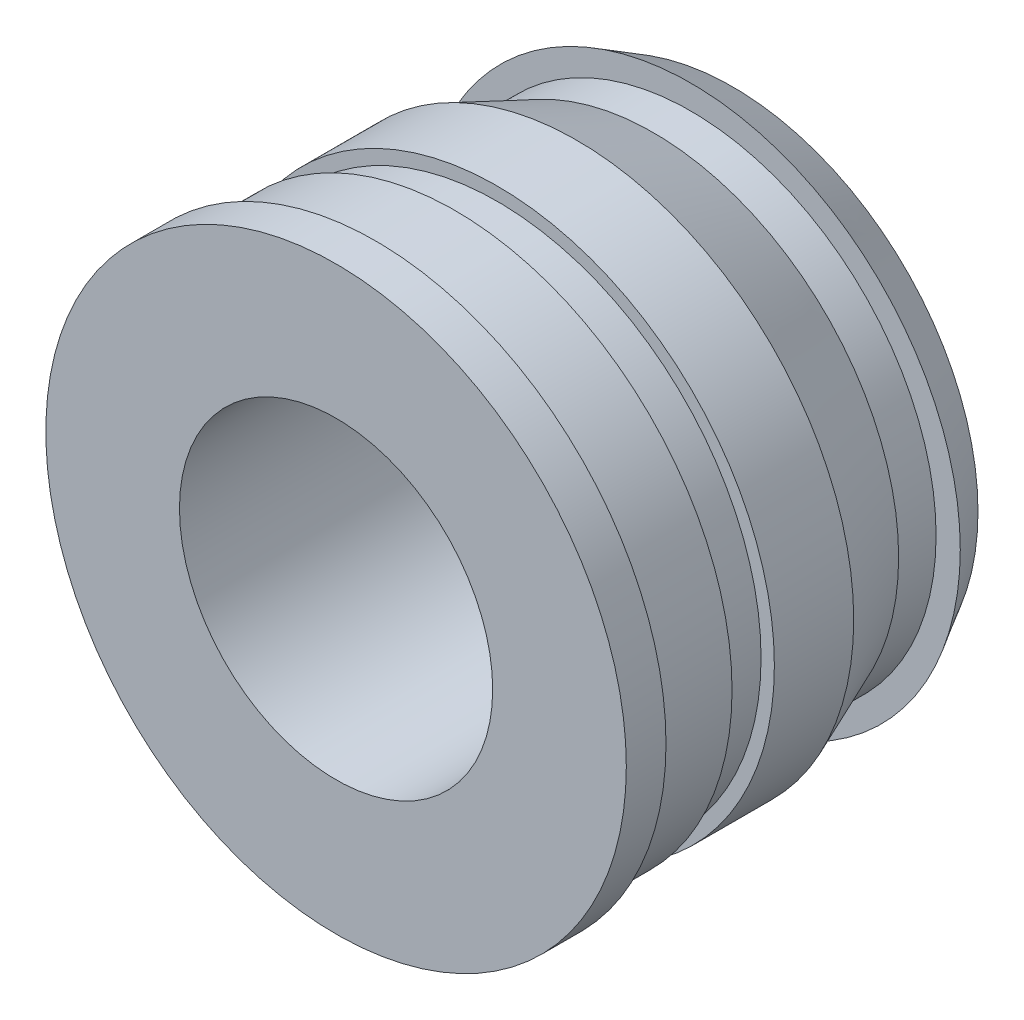
SolidWorks part; units mm, degrees
material "Brass"
ref_plane "Front Plane" through (0, 0, 0) normal (0, 0, 1) x (1, 0, 0)
ref_plane "Top Plane" through (0, 0, 0) normal (0, 1, 0) x (1, 0, 0)
ref_plane "Right Plane" through (0, 0, 0) normal (1, 0, 0) x (0, 0, -1)
sketch "Sketch1" plane through (0, 0, 0) normal (1, 0, 0) x (0, 0, -1)
  line L0 (-1.9, 0) -> (1.9, 0) construction
  line L1 (-1.9, 1.5) -> (-1.9, 2.78)
  line L2 (-1.9, 2.78) -> (-1.52, 2.78)
  line L3 (-1.52, 2.78) -> (-1.52, 2.6525)
  line L4 (-1.52, 2.6525) -> (-0.76, 2.6525)
  line L5 (-0.76, 2.6525) -> (-0.76, 2.525)
  line L6 (-0.76, 2.525) -> (-0.3545, 2.525)
  line L7 (-0.3545, 2.525) -> (-0.3545, 2.6525)
  line L9 (0.4055, 2.6525) -> (1.14, 2.3482)
  line L13 (1.14, 2.3482) -> (1.4986, 2.3482)
  line L14 (1.4986, 2.3482) -> (1.4986, 2.58)
  line L15 (1.4986, 2.58) -> (1.9, 2.3482)
  line L16 (1.9, 2.3482) -> (1.9, 1.5)
  line L17 (-1.9, 2.58) -> (1.9, 2.58) construction
  line L18 (1.9, 0) -> (1.9, 2.58) construction
  line L19 (-1.9, 0) -> (-1.9, 2.78) construction
  line L20 (-0.3545, 2.6525) -> (0.4055, 2.6525)
  line L21 (-1.9, 1.5) -> (1.9, 1.5)
  line L23 (-2.3688, 1.5541) -> (-2.1187, 1.1211) construction
  line L24 (-1.9, -2.58) -> (1.9, -2.58) construction
  line L25 (-2.1187, 1.1211) -> (-1.8687, 1.5541) construction
  line L26 (-1.8687, 1.5541) -> (-2.3688, 1.5541) construction
  line L27 (-2.3375, 1.5) -> (-1.9, 1.5) construction
  line L28 (-2.1187, 1.5541) -> (-2.1187, 1.5) construction
  line L29 (-2.1187, 1.5) -> (-2.1187, 1.1752) construction
  line L30 (-2.1187, 1.1752) -> (-2.1187, 1.1211) construction
  line L31 (-2.15, 1.1752) -> (-2.0875, 1.1752)
  line L32 (-2.3531, 1.5271) -> (-1.8844, 1.5271)
  line L33 (-2.0875, 1.1752) -> (-1.8844, 1.5271)
  line L34 (-2.15, 1.1752) -> (-2.3531, 1.5271)
  line L35 (-1.9, 2.525) -> (1.9, 2.525) construction
  line L36 (-1.9, -2.525) -> (1.9, -2.525) construction
  point P36 (-2.1187, 1.5271)
  dimension "Installed Length" = 3.8
  dimension "Dia A" = 5.56
  dimension "Dia B" = 5.16
  dimension "Thread Dia" = 3
  dimension "D6" = 30
  dimension "D8" = 0.76
  dimension "D4" = 22.5
  dimension "Thread Pitch" = 0.5
  dimension "D2" = 0.0625
  dimension "Max Hole Dia" = 5.05
  dimension "Knurling Length" = 2.66
  dimension "D1" = 4.6965
  dimension "D3" = 0.38
ref_plane "Plane1" through (0, 0, 1.52) normal (0, 0, 1) x (1, 0, 0)
sketch "Sketch2" plane through (0, 0, 1.52) normal (0, 0, 1) x (1, 0, 0)
  line L0 (0, 0) -> (0, 2.6525) construction
  line L1 (-0.1988, 2.6551) -> (0, 2.525)
  line L2 (0.1988, 2.6551) -> (0, 2.525)
  line L3 (-0.185, 2.646) -> (0, 0) construction
  line L4 (0.185, 2.646) -> (0, 0) construction
  line L5 (0, 0) -> (-0.3462, 2.6298) construction
  line L6 (0, 0) -> (0.3462, 2.6298) construction
  line L7 (0, 0) -> (1.8756, 1.8756) construction
  line L8 (0, 0) -> (0, -1.5541) construction
  line L9 (0, 0) -> (0.7771, -1.3459) construction
  circle A0 centre (0, 0) radius 2.525 construction
  circle A1 centre (0, 0) radius 2.6525 construction
  circle A3 centre (0, 0) radius 1.5541
  arc A4 (-0.1988, 2.6551) -> (0.1988, 2.6551) centre (0, 0) cw
  dimension "Knurl Angle" = 8
  dimension "Pattern Angle" = 15
  dimension "Helix Angle" = 45
  dimension "D1" = 30
sketch "Sketch3" plane through (0, 0, 0) normal (1, 0, 0) x (0, 0, -1)
  line L0 (-1.9, 1.5) -> (-1.9, 2.78) construction
  line L1 (-1.9, 2.78) -> (-1.52, 2.78) construction
  line L2 (-1.52, 2.78) -> (-1.52, 2.6525) construction
  line L3 (-1.52, 2.6525) -> (-0.76, 2.6525) construction
  line L4 (-0.76, 2.6525) -> (-0.76, 2.525) construction
  line L5 (-0.76, 2.525) -> (-0.3545, 2.525) construction
  line L6 (-0.3545, 2.525) -> (-0.3545, 2.6525) construction
  line L8 (0.4055, 2.6525) -> (1.14, 2.3482) construction
  line L12 (1.14, 2.3482) -> (1.4986, 2.3482) construction
  line L13 (1.4986, 2.3482) -> (1.4986, 2.58) construction
  line L14 (1.4986, 2.58) -> (1.9, 2.3482) construction
  line L15 (1.9, 2.3482) -> (1.9, 1.5) construction
  line L16 (-1.9, 1.5) -> (1.9, 1.5) construction
  line L17 (-1.9, 1.5) -> (-1.9, 2.78)
  line L18 (-1.9, 2.78) -> (-1.52, 2.78)
  line L19 (-1.52, 2.78) -> (-1.52, 2.6525)
  line L20 (-1.52, 2.6525) -> (-0.76, 2.6525)
  line L21 (-0.76, 2.6525) -> (-0.76, 2.525)
  line L22 (-0.76, 2.525) -> (-0.3545, 2.525)
  line L23 (-0.3545, 2.525) -> (-0.3545, 2.6525)
  line L25 (0.4055, 2.6525) -> (1.14, 2.3482)
  line L29 (1.14, 2.3482) -> (1.4986, 2.3482)
  line L30 (1.4986, 2.3482) -> (1.4986, 2.58)
  line L31 (1.4986, 2.58) -> (1.9, 2.3482)
  line L32 (1.9, 2.3482) -> (1.9, 1.5)
  line L33 (-1.9, 1.5) -> (1.9, 1.5)
  line L34 (-0.3545, 2.6525) -> (0.4055, 2.6525) construction
  line L35 (-0.3545, 2.6525) -> (0.4055, 2.6525)
revolve "Revolve1" add sketch "Sketch3" angle 360 about L0
sketch "Sketch4" [suppressed] plane through (0, 0, 1.52) normal (0, 0, 1) x (1, 0, 0)
  circle A2 centre (0, 0) radius 2.6525 construction
  circle A3 centre (0, 0) radius 2.6525
sketch "Sketch6" [suppressed] plane through (0, 0, 1.9) normal (0, 0, 1) x (1, 0, 0)
  circle A0 centre (0, 0) radius 1.5
curve "Helix/Spiral2" [suppressed] pitch 0.5 height 4.3 turns 8.6
sketch "Sketch7" [suppressed] plane through (0, 0, 0) normal (1, 0, 0) x (0, 0, -1)
  line L0 (-2.15, 1.1752) -> (-2.0875, 1.1752) construction
  line L1 (-2.15, 1.1752) -> (-2.3531, 1.5271) construction
  line L2 (-2.3531, 1.5271) -> (-1.8844, 1.5271) construction
  line L3 (-2.0875, 1.1752) -> (-1.8844, 1.5271) construction
  line L4 (-2.15, 1.1752) -> (-2.0875, 1.1752)
  line L5 (-2.15, 1.1752) -> (-2.3531, 1.5271)
  line L6 (-2.3531, 1.5271) -> (-1.8844, 1.5271)
  line L7 (-2.0875, 1.1752) -> (-1.8844, 1.5271)
sweep "Sweep1" [suppressed] add profiles "Sketch7" path "Helix/Spiral2"
sketch "Sketch8" [suppressed] plane through (0, 0, 1.9) normal (0, 0, 1) x (1, 0, 0)
  circle A0 centre (0, 0) radius 1.5541
extrude "Cut-Extrude1" [suppressed] cut sketch "Sketch8" against normal through all draft 45 and the other way through all
mirror "Mirror1" [suppressed] about plane through (0, 0, 0) normal (0, 0, 1)
curve "Helix/Spiral1" [suppressed] pitch 21.28 height 2.66 turns 0.125
sketch "Sketch5" [suppressed] plane through (0, 0, 1.52) normal (0, 0, 1) x (1, 0, 0)
  line L0 (-0.1988, 2.6551) -> (0, 2.525) construction
  line L1 (0.1988, 2.6551) -> (0, 2.525) construction
  line L2 (-0.1988, 2.6551) -> (0, 2.525)
  line L3 (0.1988, 2.6551) -> (0, 2.525)
  arc A2 (0.1988, 2.6551) -> (-0.1988, 2.6551) centre (0, 0) ccw construction
  arc A3 (0.1988, 2.6551) -> (-0.1988, 2.6551) centre (0, 0) ccw
sweep "Cut-Sweep1" [suppressed] cut profiles "Sketch5" path "Helix/Spiral1"
pattern_circular "CirPattern1" [suppressed] count 24 over 360 about axis through (0, 0, 1.9) along (0, 0, -1) of bodies 105
equation "\"D8@Sketch1\"=\"Installed Length@Sketch1\" * .2"
equation "\"D4@Helix/Spiral1\"=\"Knurling Length@Sketch1\"*(360/\"Helix Angle@Sketch2\")"
equation "\"D3@Helix/Spiral1\"=\"Knurling Length@Sketch1\""
equation "\"D1@CirPattern1\"=\"D3@CirPattern1\"/\"Pattern Angle@Sketch2\""
equation "\"D2@Sketch1\" = \"Thread Pitch@Sketch1\" / 8"
equation "\"D4@Helix/Spiral2\"=\"Thread Pitch@Sketch1\""
equation "\"D3@Helix/Spiral2\" = \"Installed Length@Sketch1\" + \"Thread Pitch@Sketch1\""
equation "\"Knurling Length@Sketch1\"=\"Installed Length@Sketch1\" * .7"
equation "\"D1@Sketch1\"=\"Max Hole Dia@Sketch1\"*.93"
equation "\"D3@Sketch1\"=\"Installed Length@Sketch1\"*.1"
